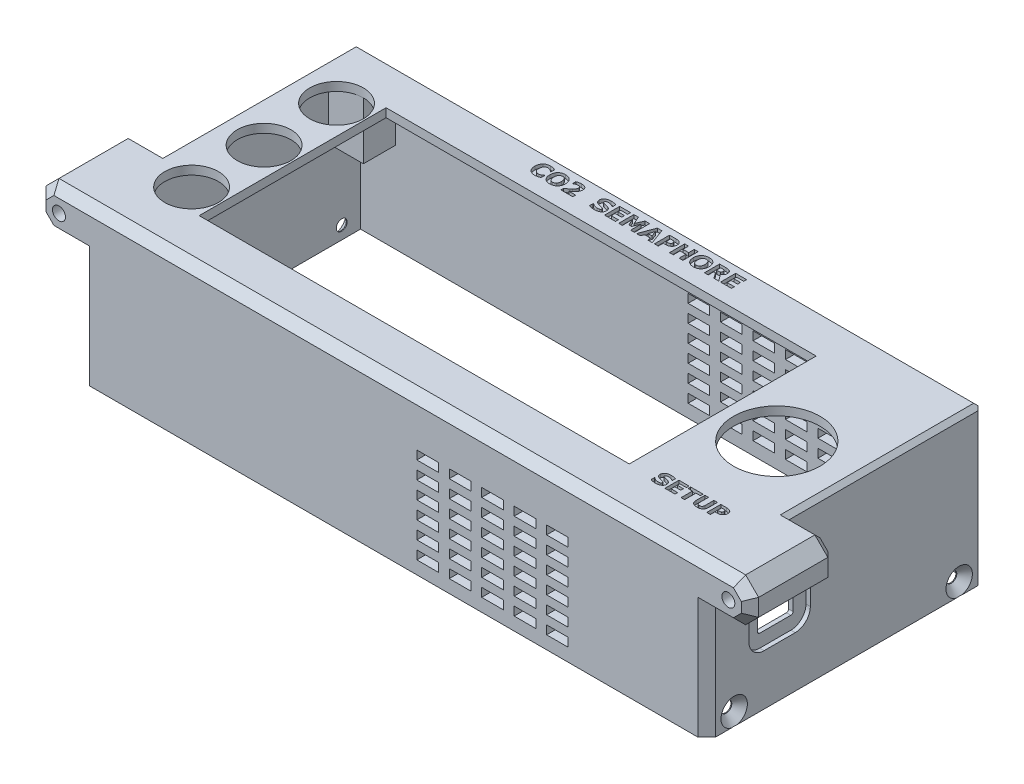
SolidWorks part; units mm, degrees
ref_plane "Спереди" through (0, 0, 0) normal (0, 0, 1) x (1, 0, 0)
ref_plane "Сверху" through (0, 0, 0) normal (0, 1, 0) x (1, 0, 0)
ref_plane "Справа" through (0, 0, 0) normal (1, 0, 0) x (0, 0, -1)
sketch "Эскиз1" plane through (0, 0, 0) normal (0, 1, 0) x (1, 0, 0)
  line L1 (-72.35, 32.35) -> (72.35, 32.35)
  line L2 (-72.35, 32.35) -> (-72.35, -32.35)
  line L3 (-72.35, -32.35) -> (72.35, -32.35)
  line L4 (72.35, 32.35) -> (72.35, -32.35)
  line L5 (-72.35, 32.35) -> (72.35, -32.35) construction
  line L6 (-72.35, -32.35) -> (72.35, 32.35) construction
  point P0 (0, 0)
  dimension "D1" = 144.7
  dimension "D2" = 64.7
extrude "Бобышка-Вытянуть1" add sketch "Эскиз1" along normal blind 36
sketch "Эскиз2" plane through (0, 0, 0) normal (0, -1, 0) x (1, 0, 0)
  line L1 (-70.35, 30.35) -> (70.35, 30.35)
  line L2 (-70.35, 30.35) -> (-70.35, -30.35)
  line L3 (-70.35, -30.35) -> (70.35, -30.35)
  line L4 (70.35, 30.35) -> (70.35, -30.35)
  line L5 (-70.35, 30.35) -> (70.35, -30.35) construction
  line L6 (-70.35, -30.35) -> (70.35, 30.35) construction
  point P0 (0, 0)
  dimension "D1" = 140.7
  dimension "D2" = 60.7
extrude "Вырез-Вытянуть1" cut sketch "Эскиз2" against normal offset from surface (34 mm away) 2 up to face at (0, 36, 0)
sketch "Эскиз3" plane through (0, 36, 0) normal (0, 1, 0) x (1, 0, 0)
  line L0 (42, 19.9) -> (-54, 19.9) construction
  line L1 (-55.7, 21.6) -> (43.7, 21.6)
  line L2 (-55.7, 21.6) -> (-55.7, -21.6)
  line L3 (-55.7, -21.6) -> (43.7, -21.6)
  line L4 (43.7, 21.6) -> (43.7, -21.6)
  line L5 (42, -19.9) -> (42, 19.9) construction
  line L6 (-54, -19.9) -> (42, -19.9) construction
  line L7 (-54, 19.9) -> (-54, -19.9) construction
  dimension "D1" = 1.7
  dimension "D2" = 1.7
  dimension "D3" = 1.7
  dimension "D4" = 1.7
extrude "Вырез-Вытянуть2" cut sketch "Эскиз3" against normal up to surface (2 mm away) up to face at (0, 34, 0)
sketch "Эскиз4" plane through (0, 36, 0) normal (0, 1, 0) x (1, 0, 0)
  circle A0 centre (-62.3, 16.75) radius 6.2
  circle A1 centre (-62.3, 0) radius 6.2
  circle A2 centre (-62.3, -16.75) radius 6.2
  dimension "D1" = 12.4
extrude "Вырез-Вытянуть3" cut sketch "Эскиз4" against normal up to surface (2 mm away) up to face at (-6, 34, 0)
sketch "Эскиз5" plane through (0, 36, 0) normal (0, 1, 0) x (1, 0, 0)
  circle A0 centre (56.2, 0) radius 10
  dimension "D1" = 20
extrude "Вырез-Вытянуть4" cut sketch "Эскиз5" against normal up to surface (2 mm away) up to face at (-62.3, 34, 6.2)
sketch "Эскиз6" plane through (72.35, 0, 0) normal (1, 0, 0) x (0, 0, -1)
  line L0 (-19.2, 16.9) -> (-19.2, 15.3) construction
  line L1 (-11.9, 14.7) -> (-19.1, 14.7)
  line L2 (-11.4, 15.2) -> (-11.4, 18.7)
  line L3 (-11.9, 19.2) -> (-19.1, 19.2)
  line L4 (-19.6, 15.2) -> (-19.6, 18.7)
  line L5 (-12, 15.1) -> (-19, 15.1) construction
  line L6 (-18.5, 18.8) -> (-12.5, 18.8) construction
  line L7 (-11.8, 16.9) -> (-11.8, 15.3) construction
  arc A0 (-11.4, 18.7) -> (-11.9, 19.2) centre (-11.9, 18.7) ccw
  arc A1 (-11.9, 14.7) -> (-11.4, 15.2) centre (-11.9, 15.2) ccw
  arc A2 (-19.1, 14.7) -> (-19.6, 15.2) centre (-19.1, 15.2) cw
  arc A3 (-19.1, 19.2) -> (-19.6, 18.7) centre (-19.1, 18.7) ccw
  dimension "D5" = 0.5
  dimension "D1" = 0.4
  dimension "D2" = 0.4
  dimension "D3" = 0.4
  dimension "D4" = 0.4
extrude "Вырез-Вытянуть5" cut sketch "Эскиз6" against normal up to surface (2 mm away) up to face at (70.35, 17, 0)
sketch "Эскиз7" plane through (72.35, 0, 0) normal (1, 0, 0) x (0, 0, -1)
  line L4 (-11.9, 19.2) -> (-19.1, 19.2) construction
  line L5 (-11.4, 15.2) -> (-11.4, 18.7) construction
  line L6 (-19.1, 14.7) -> (-11.9, 14.7) construction
  line L7 (-19.6, 18.7) -> (-19.6, 15.2) construction
  line L8 (-19.6, 18.7) -> (-19.6, 15.2) construction
  line L9 (-19.1, 14.7) -> (-11.9, 14.7) construction
  line L10 (-11.4, 15.2) -> (-11.4, 18.7) construction
  line L11 (-11.9, 19.2) -> (-19.1, 19.2) construction
  line L12 (-22.6, 18.7) -> (-22.6, 15.2)
  line L13 (-19.1, 11.7) -> (-11.9, 11.7)
  line L14 (-8.4, 15.2) -> (-8.4, 18.7)
  line L15 (-11.9, 22.2) -> (-19.1, 22.2)
  arc A0 (-11.4, 18.7) -> (-11.9, 19.2) centre (-11.9, 18.7) ccw construction
  arc A3 (-11.9, 14.7) -> (-11.4, 15.2) centre (-11.9, 15.2) ccw construction
  arc A4 (-19.6, 15.2) -> (-19.1, 14.7) centre (-19.1, 15.2) ccw construction
  arc A5 (-19.1, 19.2) -> (-19.6, 18.7) centre (-19.1, 18.7) ccw construction
  arc A6 (-19.1, 19.2) -> (-19.6, 18.7) centre (-19.1, 18.7) ccw construction
  arc A7 (-19.6, 15.2) -> (-19.1, 14.7) centre (-19.1, 15.2) ccw construction
  arc A8 (-11.9, 14.7) -> (-11.4, 15.2) centre (-11.9, 15.2) ccw construction
  arc A9 (-11.4, 18.7) -> (-11.9, 19.2) centre (-11.9, 18.7) ccw construction
  arc A10 (-22.6, 15.2) -> (-19.1, 11.7) centre (-19.1, 15.2) ccw
  arc A11 (-11.9, 11.7) -> (-8.4, 15.2) centre (-11.9, 15.2) ccw
  arc A12 (-8.4, 18.7) -> (-11.9, 22.2) centre (-11.9, 18.7) ccw
  arc A13 (-19.1, 22.2) -> (-22.6, 18.7) centre (-19.1, 18.7) ccw
  dimension "D1" = 3
extrude "Вырез-Вытянуть6" cut sketch "Эскиз7" against normal blind 1
sketch "Эскиз8" plane through (0, 34, 0) normal (0, -1, 0) x (1, 0, 0)
  circle A0 centre (-66, 26) radius 1.5
  circle A1 centre (-66, -26) radius 1.5
  circle A2 centre (66, 26) radius 1.5
  circle A3 centre (66, -26) radius 1.5
sketch "Эскиз9" plane through (0, 34, 0) normal (0, -1, 0) x (1, 0, 0)
  line L1 (-70.35, 30.35) -> (-62.3, 30.35)
  line L2 (-70.35, 30.35) -> (-70.35, 22.95)
  line L3 (-70.35, 22.95) -> (-62.3, 22.95)
  line L4 (-62.3, 30.35) -> (-62.3, 22.95)
  line L5 (-70.35, -30.35) -> (-62.3, -30.35)
  line L6 (-70.35, -30.35) -> (-70.35, -22.95)
  line L7 (-70.35, -22.95) -> (-62.3, -22.95)
  line L8 (-62.3, -30.35) -> (-62.3, -22.95)
  line L9 (70.35, 30.35) -> (62.3, 30.35)
  line L10 (70.35, 30.35) -> (70.35, 22.95)
  line L11 (70.35, 22.95) -> (62.3, 22.95)
  line L12 (62.3, 30.35) -> (62.3, 22.95)
  line L13 (70.35, -30.35) -> (62.3, -30.35)
  line L14 (70.35, -30.35) -> (70.35, -22.95)
  line L15 (70.35, -22.95) -> (62.3, -22.95)
  line L16 (62.3, -30.35) -> (62.3, -22.95)
  circle A0 centre (-62.3, 16.75) radius 6.2 construction
  circle A1 centre (-62.3, -16.75) radius 6.2 construction
  dimension "D1" = 8.05
  dimension "D2" = 8.05
extrude "Бобышка-Вытянуть2" add sketch "Эскиз9" along normal blind 13.2
sketch "Эскиз10" plane through (0, 20.8, 0) normal (0, -1, 0) x (1, 0, 0)
  circle A0 centre (66, 26) radius 1.5 construction
  circle A1 centre (66, -26) radius 1.5 construction
  circle A2 centre (-66, -26) radius 1.5 construction
  circle A3 centre (-66, 26) radius 1.5 construction
  circle A4 centre (66, 26) radius 1.5
  circle A5 centre (66, -26) radius 1.5
  circle A6 centre (-66, -26) radius 1.5
  circle A7 centre (-66, 26) radius 1.5
  circle A8 centre (-66, 26) radius 1
  circle A9 centre (-66, -26) radius 1
  circle A10 centre (66, -26) radius 1
  circle A11 centre (66, 26) radius 1
  dimension "D1" = 0.5
extrude "Вырез-Вытянуть7" cut sketch "Эскиз10" against normal up to surface (13.2 mm away) contours A8 | A9 | A10 | A11 up to face at (56.2, 34, 10)
sketch "Эскиз11" plane through (72.35, 0, 0) normal (1, 0, 0) x (0, 0, -1)
  line L1 (-32.35, 36) -> (-12.35, 36)
  line L2 (-32.35, 36) -> (-32.35, 26)
  line L3 (-32.35, 26) -> (-12.35, 26)
  line L4 (-12.35, 36) -> (-12.35, 26)
  dimension "D1" = 20
  dimension "D3" = 10
extrude "Бобышка-Вытянуть3" add sketch "Эскиз11" along normal blind 10
sketch "Эскиз12" plane through (0, 0, 32.35) normal (0, 0, 1) x (1, 0, 0)
  line L0 (79.35, 26) -> (79.35, 36) construction
  line L1 (82.35, 26) -> (72.35, 26) construction
  line L2 (-72.35, 36) -> (82.35, 36) construction
  line L3 (82.35, 29) -> (72.35, 29) construction
  line L4 (82.35, 36) -> (82.35, 26) construction
  line L5 (82.35, 33) -> (72.35, 33) construction
  line L6 (79.35, 36) -> (82.35, 33)
  line L7 (82.35, 33) -> (82.35, 36)
  line L8 (82.35, 36) -> (79.35, 36)
  line L9 (79.35, 26) -> (82.35, 29)
  line L10 (82.35, 29) -> (82.35, 26)
  line L11 (82.35, 26) -> (79.35, 26)
  dimension "D1" = 3
  dimension "D2" = 3
  dimension "D3" = 3
extrude "Вырез-Вытянуть8" cut sketch "Эскиз12" against normal up to surface (64.7 mm away) up to face at (0, 18, -32.35)
sketch "Эскиз13" plane through (-72.35, 0, 0) normal (-1, 0, 0) x (0, 0, 1)
  line L5 (32.35, 36) -> (12.35, 36)
  line L6 (32.35, 36) -> (32.35, 26)
  line L7 (32.35, 26) -> (12.35, 26)
  line L8 (12.35, 36) -> (12.35, 26)
  dimension "D1" = 10
  dimension "D3" = 20
extrude "Бобышка-Вытянуть4" add sketch "Эскиз13" along normal blind 10
sketch "Эскиз14" plane through (0, 0, 32.35) normal (0, 0, 1) x (1, 0, 0)
  line L0 (-79.35, 36) -> (-79.35, 26) construction
  line L1 (-82.35, 36) -> (79.35, 36) construction
  line L2 (-82.35, 26) -> (-72.35, 26) construction
  line L3 (-82.35, 33) -> (-72.35, 33) construction
  line L4 (-82.35, 26) -> (-82.35, 36) construction
  line L5 (-82.35, 29) -> (-72.35, 29) construction
  line L6 (-79.35, 26) -> (-82.35, 29)
  line L7 (-82.35, 29) -> (-82.35, 26)
  line L8 (-82.35, 26) -> (-79.35, 26)
  line L9 (-79.35, 36) -> (-82.35, 33)
  line L10 (-82.35, 33) -> (-82.35, 36)
  line L11 (-82.35, 36) -> (-79.35, 36)
  dimension "D1" = 3
  dimension "D2" = 3
  dimension "D3" = 3
extrude "Вырез-Вытянуть9" cut sketch "Эскиз14" against normal up to surface (64.7 mm away) up to face at (0, 18, -32.35)
sketch "Эскиз16" plane through (0, 0, 32.35) normal (0, 0, 1) x (1, 0, 0)
  line L0 (-82.35, 31) -> (82.35, 31) construction
  line L1 (-82.35, 29) -> (-82.35, 33) construction
  line L2 (82.35, 33) -> (82.35, 29) construction
  line L3 (-77.35, 36) -> (-77.35, 26) construction
  line L4 (-79.35, 36) -> (79.35, 36) construction
  line L5 (-79.35, 26) -> (-72.35, 26) construction
  line L6 (0, 36) -> (0, 0) construction
  circle A0 centre (-77.35, 31) radius 1.5
  circle A1 centre (77.35, 31) radius 1.5
  dimension "D2" = 3
  dimension "D1" = 5
extrude "Вырез-Вытянуть10" cut sketch "Эскиз16" against normal offset from surface (18 mm away) 2 up to face at (-78.0167, 31, 12.35)
sketch "Эскиз17" plane through (0, 0, -32.35) normal (0, 0, -1) x (-1, 0, 0)
  line L0 (-40.35, 36) -> (-40.35, 0) construction
  line L1 (-72.35, 36) -> (72.35, 36) construction
  line L2 (-72.35, 0) -> (72.35, 0) construction
  line L3 (-5.35, 36) -> (-5.35, 0) construction
  line L4 (-72.35, 36) -> (-72.35, 0) construction
  line L5 (-40.35, 25) -> (-5.35, 25) construction
  line L6 (-27.85, 25) -> (-27.85, 23)
  line L7 (-40.35, 25) -> (-35.35, 25)
  line L8 (-40.35, 25) -> (-40.35, 23)
  line L9 (-40.35, 23) -> (-35.35, 23)
  line L10 (-35.35, 25) -> (-35.35, 23)
  line L11 (-32.85, 25) -> (-27.85, 25)
  line L12 (-32.85, 23) -> (-27.85, 23)
  line L13 (-32.85, 25) -> (-32.85, 23)
  line L14 (-20.35, 25) -> (-20.35, 23)
  line L15 (-25.35, 25) -> (-20.35, 25)
  line L16 (-25.35, 23) -> (-20.35, 23)
  line L17 (-25.35, 25) -> (-25.35, 23)
  line L18 (-12.85, 25) -> (-12.85, 23)
  line L19 (-17.85, 25) -> (-12.85, 25)
  line L20 (-17.85, 23) -> (-12.85, 23)
  line L21 (-17.85, 25) -> (-17.85, 23)
  line L22 (-5.35, 25) -> (-5.35, 23)
  line L23 (-10.35, 25) -> (-5.35, 25)
  line L24 (-10.35, 23) -> (-5.35, 23)
  line L25 (-10.35, 25) -> (-10.35, 23)
  line L26 (-27.85, 21) -> (-27.85, 19)
  line L27 (-32.85, 21) -> (-27.85, 21)
  line L28 (-32.85, 19) -> (-27.85, 19)
  line L29 (-32.85, 21) -> (-32.85, 19)
  line L30 (-20.35, 21) -> (-20.35, 19)
  line L31 (-25.35, 21) -> (-20.35, 21)
  line L32 (-25.35, 19) -> (-20.35, 19)
  line L33 (-25.35, 21) -> (-25.35, 19)
  line L34 (-12.85, 21) -> (-12.85, 19)
  line L35 (-17.85, 21) -> (-12.85, 21)
  line L36 (-17.85, 19) -> (-12.85, 19)
  line L37 (-17.85, 21) -> (-17.85, 19)
  line L38 (-5.35, 21) -> (-5.35, 19)
  line L39 (-10.35, 21) -> (-5.35, 21)
  line L40 (-10.35, 19) -> (-5.35, 19)
  line L41 (-10.35, 21) -> (-10.35, 19)
  line L42 (-27.85, 17) -> (-27.85, 15)
  line L43 (-32.85, 17) -> (-27.85, 17)
  line L44 (-32.85, 15) -> (-27.85, 15)
  line L45 (-32.85, 17) -> (-32.85, 15)
  line L46 (-20.35, 17) -> (-20.35, 15)
  line L47 (-25.35, 17) -> (-20.35, 17)
  line L48 (-25.35, 15) -> (-20.35, 15)
  line L49 (-25.35, 17) -> (-25.35, 15)
  line L50 (-12.85, 17) -> (-12.85, 15)
  line L51 (-17.85, 17) -> (-12.85, 17)
  line L52 (-17.85, 15) -> (-12.85, 15)
  line L53 (-17.85, 17) -> (-17.85, 15)
  line L54 (-5.35, 17) -> (-5.35, 15)
  line L55 (-10.35, 17) -> (-5.35, 17)
  line L56 (-10.35, 15) -> (-5.35, 15)
  line L57 (-10.35, 17) -> (-10.35, 15)
  line L58 (-27.85, 13) -> (-27.85, 11)
  line L59 (-32.85, 13) -> (-27.85, 13)
  line L60 (-32.85, 11) -> (-27.85, 11)
  line L61 (-32.85, 13) -> (-32.85, 11)
  line L62 (-20.35, 13) -> (-20.35, 11)
  line L63 (-25.35, 13) -> (-20.35, 13)
  line L64 (-25.35, 11) -> (-20.35, 11)
  line L65 (-25.35, 13) -> (-25.35, 11)
  line L66 (-12.85, 13) -> (-12.85, 11)
  line L67 (-17.85, 13) -> (-12.85, 13)
  line L68 (-17.85, 11) -> (-12.85, 11)
  line L69 (-17.85, 13) -> (-17.85, 11)
  line L70 (-5.35, 13) -> (-5.35, 11)
  line L71 (-10.35, 13) -> (-5.35, 13)
  line L72 (-10.35, 11) -> (-5.35, 11)
  line L73 (-10.35, 13) -> (-10.35, 11)
  line L74 (-27.85, 9) -> (-27.85, 7)
  line L75 (-32.85, 9) -> (-27.85, 9)
  line L76 (-32.85, 7) -> (-27.85, 7)
  line L77 (-32.85, 9) -> (-32.85, 7)
  line L78 (-20.35, 9) -> (-20.35, 7)
  line L79 (-25.35, 9) -> (-20.35, 9)
  line L80 (-25.35, 7) -> (-20.35, 7)
  line L81 (-25.35, 9) -> (-25.35, 7)
  line L82 (-12.85, 9) -> (-12.85, 7)
  line L83 (-17.85, 9) -> (-12.85, 9)
  line L84 (-17.85, 7) -> (-12.85, 7)
  line L85 (-17.85, 9) -> (-17.85, 7)
  line L86 (-5.35, 9) -> (-5.35, 7)
  line L87 (-10.35, 9) -> (-5.35, 9)
  line L88 (-10.35, 7) -> (-5.35, 7)
  line L89 (-10.35, 9) -> (-10.35, 7)
  line L90 (-27.85, 5) -> (-27.85, 3)
  line L91 (-32.85, 5) -> (-27.85, 5)
  line L92 (-32.85, 3) -> (-27.85, 3)
  line L93 (-32.85, 5) -> (-32.85, 3)
  line L94 (-20.35, 5) -> (-20.35, 3)
  line L95 (-25.35, 5) -> (-20.35, 5)
  line L96 (-25.35, 3) -> (-20.35, 3)
  line L97 (-25.35, 5) -> (-25.35, 3)
  line L98 (-12.85, 5) -> (-12.85, 3)
  line L99 (-17.85, 5) -> (-12.85, 5)
  line L100 (-17.85, 3) -> (-12.85, 3)
  line L101 (-17.85, 5) -> (-17.85, 3)
  line L102 (-5.35, 5) -> (-5.35, 3)
  line L103 (-10.35, 5) -> (-5.35, 5)
  line L104 (-10.35, 3) -> (-5.35, 3)
  line L105 (-10.35, 5) -> (-10.35, 3)
  line L106 (-35.35, 21) -> (-35.35, 19)
  line L107 (-40.35, 21) -> (-35.35, 21)
  line L108 (-40.35, 19) -> (-35.35, 19)
  line L109 (-40.35, 21) -> (-40.35, 19)
  line L110 (-35.35, 17) -> (-35.35, 15)
  line L111 (-40.35, 17) -> (-35.35, 17)
  line L112 (-40.35, 15) -> (-35.35, 15)
  line L113 (-40.35, 17) -> (-40.35, 15)
  line L114 (-35.35, 13) -> (-35.35, 11)
  line L115 (-40.35, 13) -> (-35.35, 13)
  line L116 (-40.35, 11) -> (-35.35, 11)
  line L117 (-40.35, 13) -> (-40.35, 11)
  line L118 (-35.35, 9) -> (-35.35, 7)
  line L119 (-40.35, 9) -> (-35.35, 9)
  line L120 (-40.35, 7) -> (-35.35, 7)
  line L121 (-40.35, 9) -> (-40.35, 7)
  line L122 (-35.35, 5) -> (-35.35, 3)
  line L123 (-40.35, 5) -> (-35.35, 5)
  line L124 (-40.35, 3) -> (-35.35, 3)
  line L125 (-40.35, 5) -> (-40.35, 3)
  dimension "D1" = 32
  dimension "D2" = 35
  dimension "D3" = 25
  dimension "D4" = 5
  dimension "D5" = 2
  dimension "D6" = 5
  dimension "D7" = 6
extrude "Вырез-Вытянуть11" cut sketch "Эскиз17" against normal up to surface (64.7 mm away) up to face at (75.85, 31, 32.35)
chamfer "Фаска1" distance 2 angle 45 4 edges at (72.35, 13, 32.35) (72.35, 18, -32.35) (-72.35, 18, -32.35) (-72.35, 13, 32.35)
chamfer "Фаска2" distance 2 angle 45 1 edges at (0, 36, -32.35)
chamfer "Фаска3" distance 2 angle 45 9 edges at (74.85, 26, 32.35) (80.85, 27.5, 32.35) (82.35, 31, 32.35) (80.85, 34.5, 32.35) (-74.85, 26, 32.35) (-80.85, 27.5, 32.35) (-82.35, 31, 32.35) (-80.85, 34.5, 32.35) (0, 36, 32.35)
sketch "Эскиз18" plane through (0, 36, 0) normal (0, 1, 0) x (1, 0, 0)
  line L0 (46.1, -22.35) -> (72.35, -22.35) construction
  line L1 (46.1, -16.8) -> (46.1, -22.3) construction
  line L2 (72.35, -12.35) -> (72.35, 30.35) construction
  line L3 (78.5216, -32.35) -> (-78.5216, -32.35) construction
  text T0 "  SETUP" font "Verdana" height in points 12
  dimension "D1" = 10
extrude "Вырез-Вытянуть12" cut sketch "Эскиз18" against normal blind 0.8
chamfer "Фаска4" distance 1 angle 45 2 edges at (-72.35, 36, -9) (72.35, 36, -9)
sketch "Эскиз19" plane through (-70.35, 0, 0) normal (1, 0, 0) x (0, 0, -1)
  circle A0 centre (-26, 3) radius 1.25
  circle A1 centre (26, 3) radius 1.25
extrude "Вырез-Вытянуть13" cut sketch "Эскиз19" against normal up to surface and the other way up to surface
chamfer "Фаска5" distance 1.8 angle 45 4 edges at (72.35, 3, -24.75) (72.35, 3, 27.25) (-72.35, 3, 24.75) (-72.35, 3, -27.25)
sketch "Эскиз20" plane through (0, 36, 0) normal (0, 1, 0) x (1, 0, 0)
  line L0 (71.35, 25.35) -> (-79.35, 25.35) construction
  line L1 (71.35, -12.35) -> (71.35, 30.35) construction
  line L4 (-70.35, 32.35) -> (70.35, 32.35) construction
  line L5 (-79.35, -12.35) -> (-79.35, -30.35) construction
  text T0 " CO2  SEMAPHORE" font "Verdana" height 3.5
  dimension "D1" = 7
extrude "Вырез-Вытянуть14" cut sketch "Эскиз20" against normal blind 0.8
chamfer "Фаска6" distance 2 angle 45 12 edges at (71.85, 35.5, 12.35) (-71.85, 35.5, 12.35) (82.35, 31, 12.35) (75.85, 26, 12.35) (80.85, 27.5, 12.35) (75.35, 36, 12.35) (80.85, 34.5, 12.35) (-82.35, 31, 12.35) (-75.35, 36, 12.35) (-80.85, 34.5, 12.35) (-75.85, 26, 12.35) (-80.85, 27.5, 12.35)
